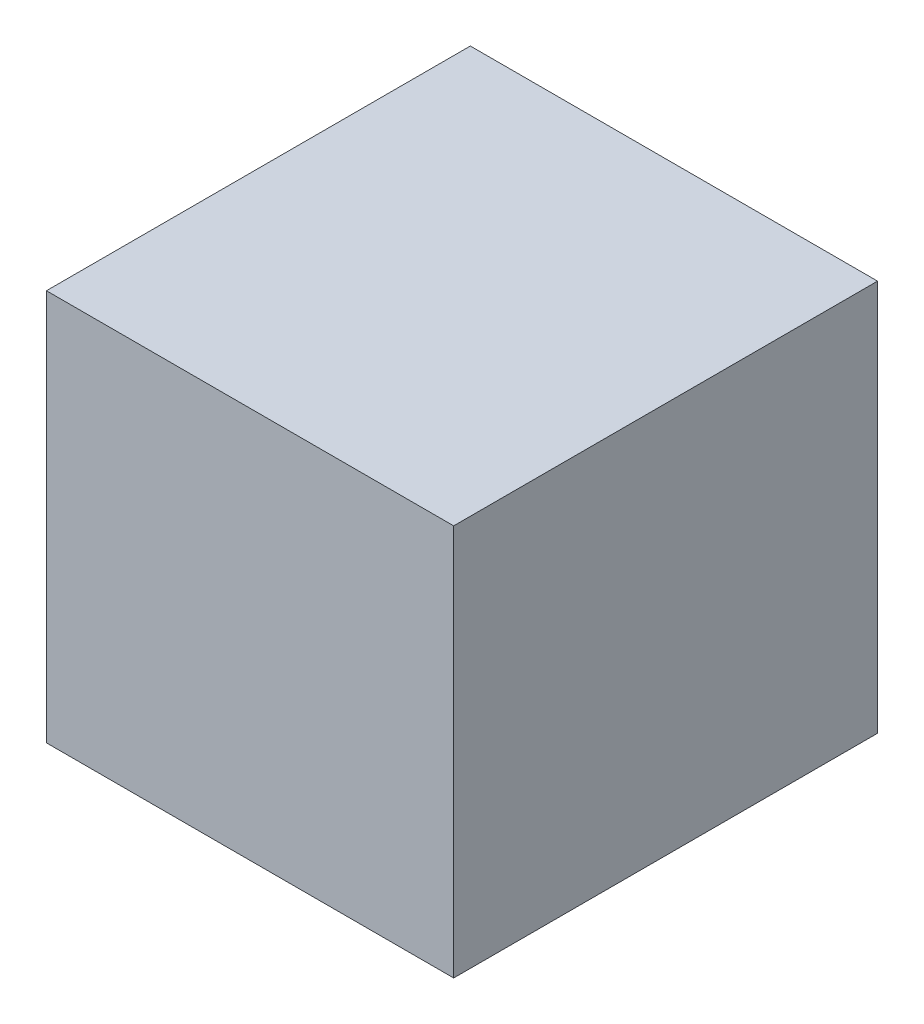
SolidWorks part; units mm, degrees
ref_plane "Front Plane" through (0, 0, 0) normal (0, 0, 1) x (1, 0, 0)
ref_plane "Top Plane" through (0, 0, 0) normal (0, 1, 0) x (1, 0, 0)
ref_plane "Right Plane" through (0, 0, 0) normal (1, 0, 0) x (0, 0, -1)
sketch "Sketch1" plane through (0, 0, 0) normal (0, 0, 1) x (1, 0, 0)
  line L1 (0, 0) -> (31.7045, 0)
  line L2 (0, 0) -> (0, 30.4851)
  line L3 (0, 30.4851) -> (31.7045, 30.4851)
  line L4 (31.7045, 0) -> (31.7045, 30.4851)
extrude "Boss-Extrude1" add sketch "Sketch1" along normal blind 33
